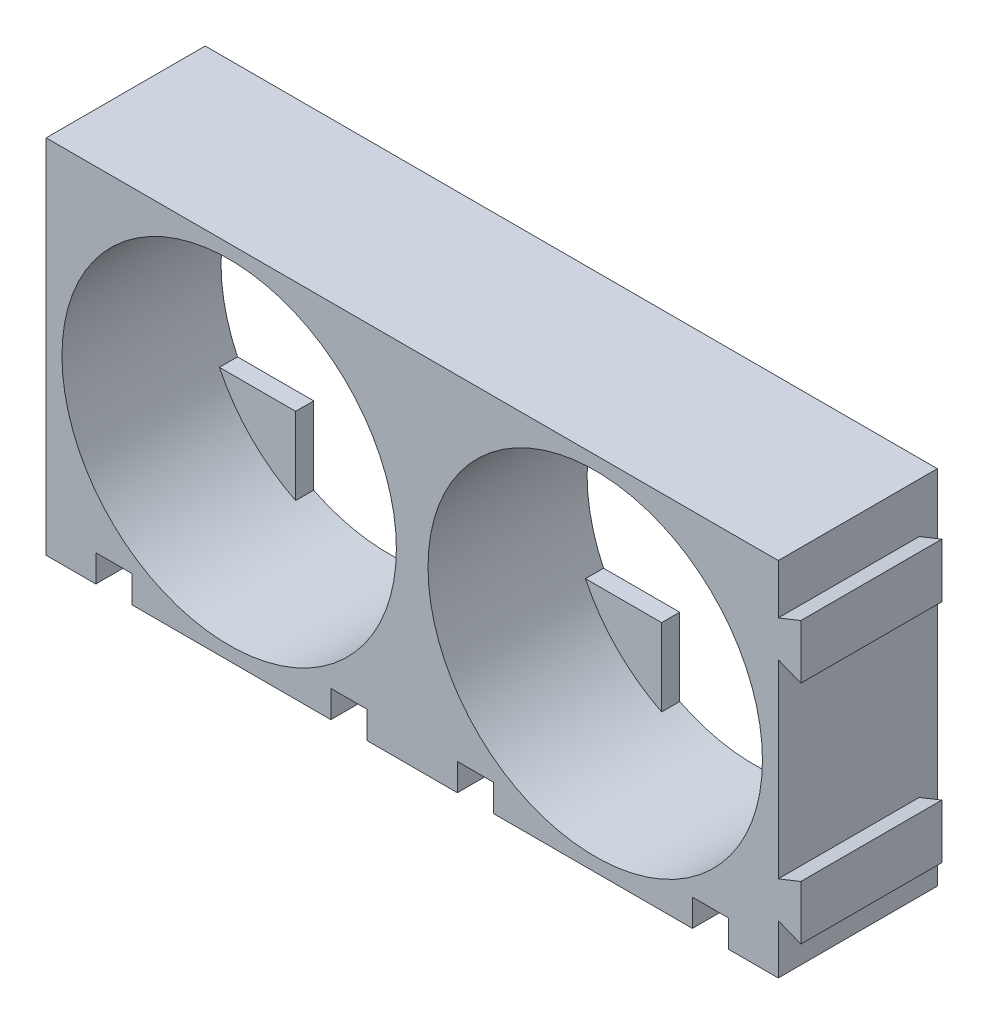
SolidWorks part; units mm, degrees
ref_plane "Front Plane" through (0, 0, 0) normal (0, 0, 1) x (1, 0, 0)
ref_plane "Top Plane" through (0, 0, 0) normal (0, 1, 0) x (1, 0, 0)
ref_plane "Right Plane" through (0, 0, 0) normal (1, 0, 0) x (0, 0, -1)
sketch "Sketch1" plane through (0, 0, 0) normal (0, 0, 1) x (1, 0, 0)
  line L0 (55, 0) -> (-55, 0) construction
  line L1 (-20.25, 10) -> (20.25, 10)
  line L2 (-20.25, 10) -> (-20.25, -10)
  line L3 (-20.25, -10) -> (20.25, -10)
  line L4 (20.25, 10) -> (20.25, -10)
  line L5 (-20.25, 10) -> (20.25, -10) construction
  line L6 (-20.25, -10) -> (20.25, 10) construction
  circle A0 centre (-10.125, 0) radius 9.25
  circle A1 centre (10.125, 0) radius 9.25
  point P0 (0, 0)
  dimension "D3" = 18.5
  dimension "D4" = 18.5
  dimension "D1" = 20
  dimension "D2" = 40.5
  dimension "D5" = 20.25
  dimension "D6" = 10.125
extrude "Boss-Extrude1" add sketch "Sketch1" along normal blind 8.8
sketch "Sketch2" plane through (0, -10, 0) normal (0, -1, 0) x (1, 0, 0)
  line L0 (-20.25, 8.8) -> (20.25, 8.8) construction
  line L1 (-17.5, 8.8) -> (-15.5, 8.8)
  line L2 (-17.5, 8.8) -> (-17.5, 1)
  line L3 (-17.5, 1) -> (-15.5, 1)
  line L4 (-15.5, 8.8) -> (-15.5, 1)
  line L5 (-20.25, 8.8) -> (-20.25, 0) construction
  line L6 (11, 0) -> (-11, 0) construction
  line L7 (-4.5, 8.8) -> (-2.5, 8.8)
  line L8 (-4.5, 8.8) -> (-4.5, 1)
  line L9 (-4.5, 1) -> (-2.5, 1)
  line L10 (-2.5, 8.8) -> (-2.5, 1)
  line L16 (0, -4.84) -> (0, 4.84) construction
  line L17 (4.5, 1) -> (2.5, 1)
  line L18 (2.5, 8.8) -> (2.5, 1)
  line L19 (4.5, 8.8) -> (2.5, 8.8)
  line L20 (4.5, 8.8) -> (4.5, 1)
  line L21 (17.5, 1) -> (15.5, 1)
  line L22 (15.5, 8.8) -> (15.5, 1)
  line L23 (17.5, 8.8) -> (15.5, 8.8)
  line L24 (17.5, 8.8) -> (17.5, 1)
  dimension "D1" = 2.75
  dimension "D2" = 2
  dimension "D3" = 11
  dimension "D4" = 2
  dimension "D5" = 1
extrude "Cut-Extrude1" cut sketch "Sketch2" against normal blind 1.5
sketch "Sketch3" plane through (0, 0, 0) normal (0, 0, -1) x (-1, 0, 0)
  line L0 (-1.7846, 4) -> (-6, 4)
  line L3 (-18.4654, 4) -> (-14.25, 4)
  line L4 (-14.25, 8.2793) -> (-14.25, 4)
  line L7 (6, 4) -> (1.7846, 4)
  line L8 (-6, 8.2793) -> (-6, 4)
  line L11 (4.84, 0) -> (-4.84, 0) construction
  line L12 (0, -10) -> (0, -4)
  line L14 (-6, -8.2793) -> (-6, -4)
  line L15 (6, -4) -> (1.7846, -4)
  line L16 (-18.4654, -4) -> (-14.25, -4)
  line L17 (-14.25, -8.2793) -> (-14.25, -4)
  line L20 (0, 4.84) -> (0, -4.84) construction
  line L21 (20.25, -10) -> (20.25, -4)
  line L22 (20.25, -10) -> (14.25, -10)
  line L23 (14.25, -8.2793) -> (14.25, -4)
  line L24 (18.4654, -4) -> (14.25, -4)
  line L25 (6, -8.2793) -> (6, -4)
  line L26 (6, 8.2793) -> (6, 4)
  line L27 (18.4654, 4) -> (14.25, 4)
  line L28 (14.25, 8.2793) -> (14.25, 4)
  line L31 (-1.7846, -4) -> (-6, -4)
  circle A0 centre (10.125, 0) radius 9.25 construction
  circle A1 centre (-10.125, 0) radius 9.25 construction
  arc A2 (1.7846, -4) -> (6, -8.2793) centre (10.125, 0) ccw
  arc A3 (-18.4654, -4) -> (-14.25, -8.2793) centre (-10.125, 0) ccw
  arc A4 (-14.25, 8.2793) -> (-18.4654, 4) centre (-10.125, 0) ccw
  arc A5 (-1.7846, 4) -> (-6, 8.2793) centre (-10.125, 0) ccw
  arc A6 (-6, -8.2793) -> (-1.7846, -4) centre (-10.125, 0) ccw
  arc A7 (14.25, -8.2793) -> (18.4654, -4) centre (10.125, 0) ccw
  arc A8 (18.4654, 4) -> (14.25, 8.2793) centre (10.125, 0) ccw
  arc A9 (6, 8.2793) -> (1.7846, 4) centre (10.125, 0) ccw
  circle M26 centre (10.125, 0) radius 9.25
  circle M27 centre (-10.125, 0) radius 9.25
extrude "Boss-Extrude2" add sketch "Sketch3" against normal blind 1 contours L4 L3 M27 | L8 L0 M27 | L31 L14 M27 | L17 L16 M27 | L26 L7 M26 | L28 L27 M26 | L24 L23 M26 | L25 L15 M26 region at (4.4402, 5.5826, 0) region at (15.8098, 5.5826, 0) region at (4.4402, -5.5826, 0) region at (15.8098, -5.5826, 0) region at (-4.4402, 5.5826, 0) region at (-4.4402, -5.5826, 0) region at (-15.8098, 5.5826, 0) region at (-15.8098, -5.5826, 0)
sketch "Sketch4" plane through (20.25, 0, 0) normal (1, 0, 0) x (0, 0, -1)
  line L0 (-8.8, -10) -> (-8.8, 10) construction
  line L1 (-8.8, 7.25) -> (-1, 7.25)
  line L2 (-8.8, 7.25) -> (-8.8, 5.25)
  line L3 (-8.8, 5.25) -> (-1, 5.25)
  line L4 (-1, 7.25) -> (-1, 5.25)
  line L5 (0, 11) -> (0, -11) construction
  line L6 (-8.8, 10) -> (0, 10) construction
  line L7 (4.84, 0) -> (-4.84, 0) construction
  line L8 (-8.8, -5.25) -> (-1, -5.25)
  line L9 (-1, -7.25) -> (-1, -5.25)
  line L10 (-8.8, -7.25) -> (-1, -7.25)
  line L11 (-8.8, -7.25) -> (-8.8, -5.25)
  dimension "D1" = 1
  dimension "D2" = 2.75
  dimension "D3" = 2
ref_plane "Plane1" through (21.5, 0, 0) normal (1, 0, 0) x (0, 0, -1)
sketch "Sketch5" plane through (21.5, 0, 0) normal (1, 0, 0) x (0, 0, -1)
  line L0 (-8.8, -10) -> (-8.8, 10) construction
  line L1 (-8.8, 7.75) -> (-1, 7.75)
  line L2 (-8.8, 7.75) -> (-8.8, 4.75)
  line L3 (-8.8, 4.75) -> (-1, 4.75)
  line L4 (-1, 7.75) -> (-1, 4.75)
  line L5 (-1, 7.25) -> (-1, 5.25) construction
  line L6 (-8.8, 7.25) -> (-1, 7.25) construction
  line L7 (4.84, 0) -> (-4.84, 0) construction
  line L8 (-8.8, -4.75) -> (-1, -4.75)
  line L9 (-1, -7.75) -> (-1, -4.75)
  line L10 (-8.8, -7.75) -> (-1, -7.75)
  line L11 (-8.8, -7.75) -> (-8.8, -4.75)
  dimension "D1" = 3
  dimension "D2" = 0.5
loft "Loft1" add section "Sketch4" section "Sketch5"
loft "Loft2" add section "Sketch4<3>" section "Sketch5<3>"
sketch "Sketch4<3>" plane through (20.25, 0, 0) normal (1, 0, 0) x (0, 0, -1) same geometry as "Sketch4"
sketch "Sketch5<3>" plane through (21.5, 0, 0) normal (1, 0, 0) x (0, 0, -1) same geometry as "Sketch5"
